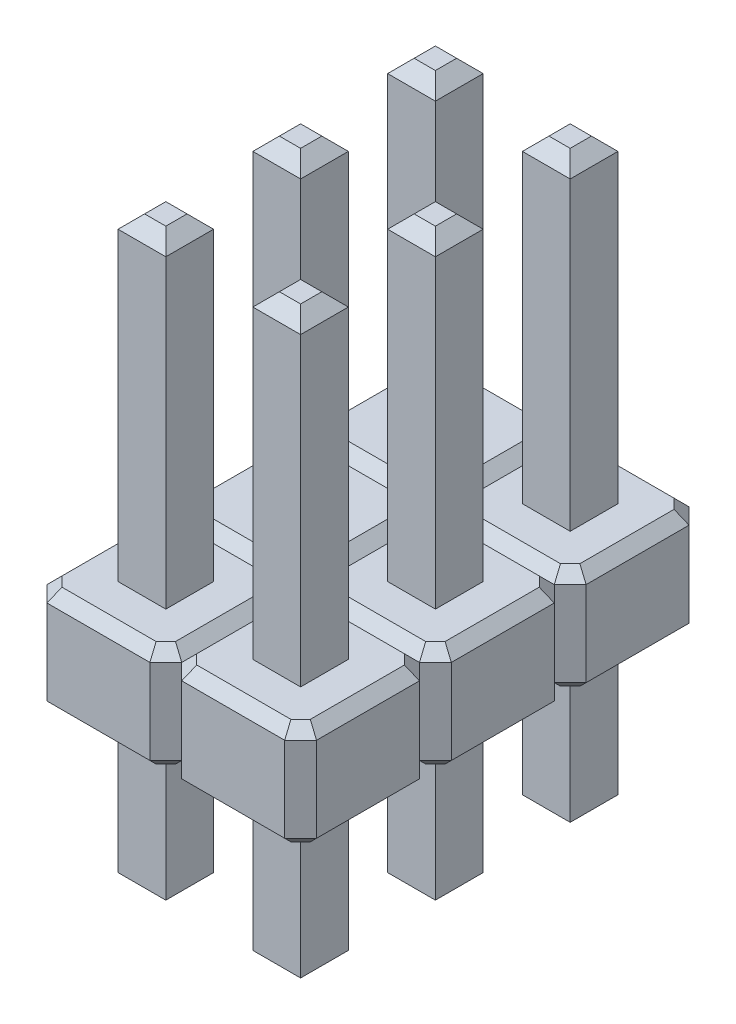
SolidWorks part; units mm, degrees
note: The reader was unsure of these and kept them because the rebuilt part matched: shared geometry of "Эскиз1<3>".
other "PIN1"
other "PIN3"
other "PIN5"
other "PIN2"
other "PIN4"
other "PIN6"
other "PLASTIC" parameters "D1"=27.9408, "D4"=1.6296, "D5"=1.1205, "D9"=0.3, "D10"=0.3, "D11"=0.3, "D12"=0.3, "D8"=0.5
ref_plane "Спереди" through (0, 0, 0) normal (0, 0, 1) x (1, 0, 0)
ref_plane "Сверху" through (0, 0, 0) normal (0, 1, 0) x (1, 0, 0)
ref_plane "Справа" through (0, 0, 0) normal (1, 0, 0) x (0, 0, -1)
sketch "Эскиз1" plane through (0, 0, 0) normal (0, 1, 0) x (1, 0, 0)
  line L1 (-0.45, -0.45) -> (0.45, -0.45)
  line L2 (-0.45, -0.45) -> (-0.45, 0.45)
  line L3 (-0.45, 0.45) -> (0.45, 0.45)
  line L4 (0.45, -0.45) -> (0.45, 0.45)
  line L5 (-0.45, -0.45) -> (0.45, 0.45) construction
  line L6 (-0.45, 0.45) -> (0.45, -0.45) construction
  line L26 (0.97, -1.27) -> (1.27, -0.97)
  line L27 (-0.97, -1.27) -> (0.97, -1.27)
  line L28 (-1.27, -0.97) -> (-1.27, 0.97)
  line L29 (-0.97, 1.27) -> (0.97, 1.27)
  line L30 (1.27, -0.97) -> (1.27, 0.97)
  line L31 (-1.27, -1.27) -> (1.27, 1.27) construction
  line L32 (-1.27, 1.27) -> (1.27, -1.27) construction
  line L33 (-0.97, -1.27) -> (-1.27, -0.97)
  line L34 (-1.27, 0.97) -> (-0.97, 1.27)
  line L35 (1.27, 0.97) -> (0.97, 1.27)
  circle A0 centre (0, 0) radius 0.45 construction
  dimension "D1" = 0.9
  dimension "D4" = 1.27
  dimension "D5" = 1.27
extrude "metal part" add sketch "Эскиз1" along normal blind 11 contours L1 L4 L3 L2
extrude "plastic part" add sketch "Эскиз1<3>" along direction (0, -1, 0) on the side of the normal blind 2 from offset 3 separate body contours L30 L35 L29 L34 L28 L33 L27 L26 L4 L1 L2 L3
sketch "Эскиз1<3>" plane through (0, 0, 0) normal (0, 1, 0) x (1, 0, 0) same geometry as "Эскиз1"
chamfer "Фаска1" distance 0.2 angle 45 16 edges at (1.12, 3, -1.12) (1.27, 3, 0) (1.12, 3, 1.12) (0, 3, 1.27) (-1.12, 3, 1.12) (-1.27, 3, 0) (-1.12, 3, -1.12) (0, 3, -1.27) (1.12, 5, -1.12) (0, 5, -1.27) (-1.12, 5, -1.12) (-1.27, 5, 0) (-1.12, 5, 1.12) (1.27, 5, 0) (1.12, 5, 1.12) (0, 5, 1.27) tangent propagation no
chamfer "Фаска2" distance 0.25 angle 45 8 edges at (0, 0, 0.45) (0.45, 0, 0) (0, 0, -0.45) (-0.45, 0, 0) (0.45, 11, 0) (0, 11, -0.45) (0, 11, 0.45) (-0.45, 11, 0)
pattern_linear "Линейный массив1" count 3 spacing 2.54 along (0, 0, -1) count 2 spacing 2.54 along (1, 0, 0) of bodies 103 104
combine bodies "Соединить2" operation type add bodies to combine 113 116 117 114 104 115
equation "\"D5@Эскиз1\"=\"D4@Эскиз1\""
